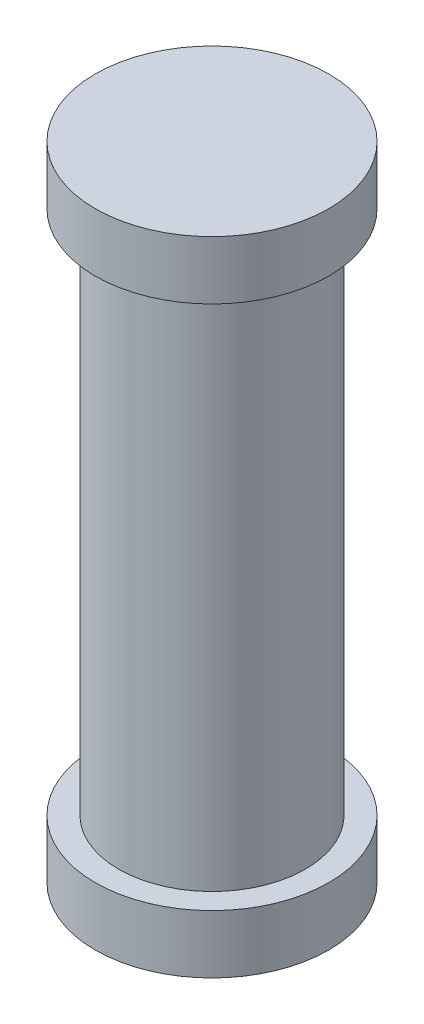
SolidWorks part; units mm, degrees
ref_plane "Front Plane" through (0, 0, 0) normal (0, 0, 1) x (1, 0, 0)
ref_plane "Top Plane" through (0, 0, 0) normal (0, 1, 0) x (1, 0, 0)
ref_plane "Right Plane" through (0, 0, 0) normal (1, 0, 0) x (0, 0, -1)
sketch "Sketch1" plane through (0, 0, 0) normal (0, 1, 0) x (1, 0, 0)
  circle A0 centre (0, 0) radius 2
extrude "Boss-Extrude1" add sketch "Sketch1" along normal blind 1
sketch "Sketch2" plane through (0, 1, 0) normal (0, 1, 0) x (1, 0, 0)
  circle A0 centre (0, 0) radius 1.6
extrude "Boss-Extrude2" add sketch "Sketch2" along normal blind 9
sketch "Sketch3" plane through (0, 10, 0) normal (0, 1, 0) x (1, 0, 0)
  circle A0 centre (0, 0) radius 2
extrude "Boss-Extrude3" add sketch "Sketch3" along normal blind 1
